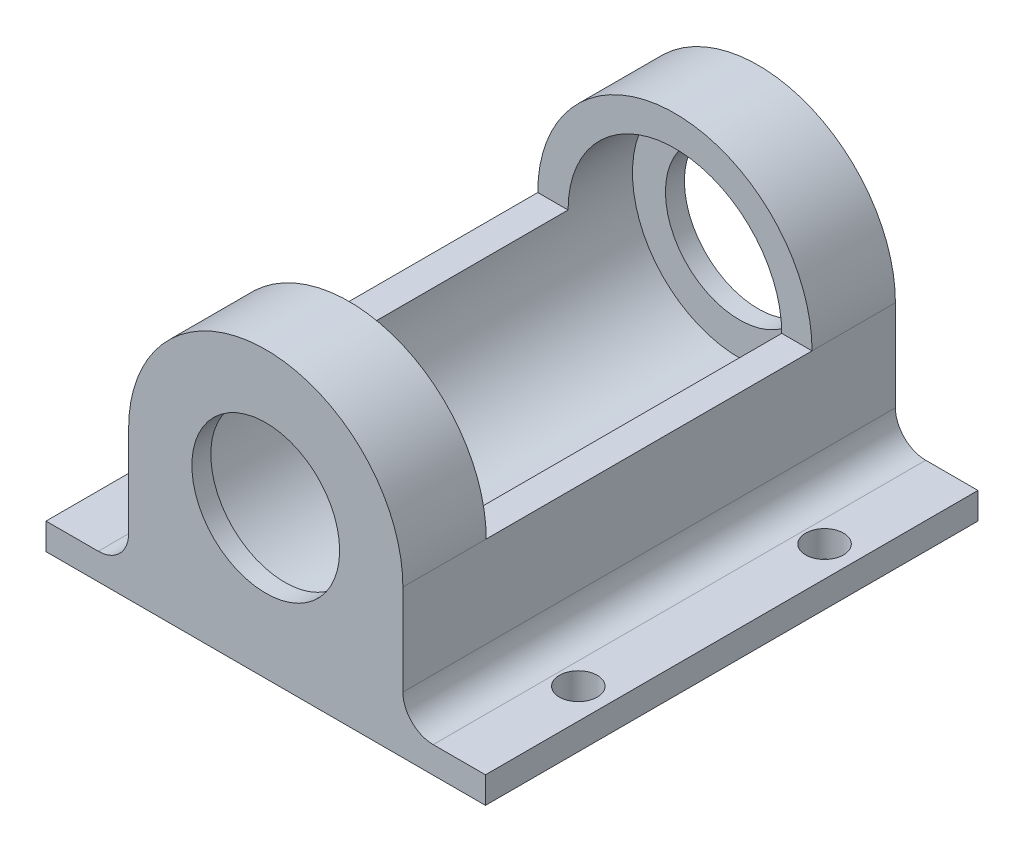
SolidWorks part; units mm, degrees
ref_plane "Front Plane" through (0, 0, 0) normal (0, 0, 1) x (1, 0, 0)
ref_plane "Top Plane" through (0, 0, 0) normal (0, 1, 0) x (1, 0, 0)
ref_plane "Right Plane" through (0, 0, 0) normal (1, 0, 0) x (0, 0, -1)
sketch "Sketch1" plane through (0, 0, 0) normal (0, 1, 0) x (1, 0, 0)
  line L0 (-43.3727, 0) -> (41.7261, 0) construction
  line L1 (-29, -32.5) -> (29, -32.5)
  line L2 (-29, -32.5) -> (-29, 32.5)
  line L3 (-29, 32.5) -> (29, 32.5)
  line L4 (29, -32.5) -> (29, 32.5)
  line L5 (-29, -32.5) -> (29, 32.5) construction
  line L6 (-29, 32.5) -> (29, -32.5) construction
  line L7 (-29, -16.25) -> (29, -16.25) construction
  line L8 (-29, 16.25) -> (29, 16.25) construction
  circle A0 centre (-25, -16.25) radius 2.5
  circle A1 centre (25, -16.25) radius 2.5
  circle A2 centre (25, 16.25) radius 2.5
  circle A3 centre (-25, 16.25) radius 2.5
  point P0 (0, 0)
  dimension "D3" = 5
  dimension "D5" = 5
  dimension "D11" = 5
  dimension "D12" = 5
  dimension "D1" = 65
  dimension "D2" = 58
  dimension "D4" = 4
  dimension "D6" = 4
  dimension "D7" = 16.25
  dimension "D8" = 16.25
  dimension "D9" = 4
  dimension "D10" = 4
extrude "Boss-Extrude1" add sketch "Sketch1" along normal blind 3.5
sketch "Sketch2" plane through (0, 0, 32.5) normal (0, 0, 1) x (1, 0, 0)
  line L0 (0, -11.0181) -> (0, 49.5169) construction
  line L1 (-29, 3.5) -> (29, 3.5) construction
  line L2 (-41.9601, 19.5) -> (50.3847, 19.5) construction
  line L3 (-18.1, 19.5) -> (-18.1, 3.5)
  line L4 (18.1, 19.5) -> (18.1, 3.5)
  circle A0 centre (0, 19.5) radius 14.1
  circle A1 centre (0, 19.5) radius 9.75
  arc A2 (-18.1, 19.5) -> (18.1, 19.5) centre (0, 19.5) cw
  line M5 (29, 3.5) -> (-29, 3.5)
  dimension "D1" = 28.2
  dimension "D3" = 19.5
  dimension "D6" = 4
  dimension "D2" = 16
extrude "Boss-Extrude2" add sketch "Sketch2" against normal blind 2.5 contours A2 L3 L4 A0 M5 | A0 A1 region at (0, 37.1027, 32.5) region at (-13.7012, 19.5, 32.5)
extrude "Boss-Extrude3" add sketch "Sketch2<3>" against normal blind 11 contours A2 L3 L4 A0 M5 region at (0, 37.1027, 32.5)
sketch "Sketch2<3>" plane through (0, 0, 32.5) normal (0, 0, 1) x (1, 0, 0) same geometry as "Sketch2"
extrude "Boss-Extrude4" add sketch "Sketch2<4>" along normal blind 11 from offset 65 contours A2 L3 L4 A0 M5 region at (0, 37.1027, 32.5) offset against normal yes
sketch "Sketch2<4>" plane through (0, 0, 32.5) normal (0, 0, 1) x (1, 0, 0) same geometry as "Sketch2"
extrude "Boss-Extrude5" add sketch "Sketch2<5>" along normal blind 2.5 from surface contours A0 A1 region at (-13.7012, 19.5, 32.5) starting at face at (0, 8.8875, -32.5)
sketch "Sketch2<5>" plane through (0, 0, 32.5) normal (0, 0, 1) x (1, 0, 0) same geometry as "Sketch2"
fillet "Fillet3" radius 4 4 edges at (-18.1, 3.5, 27) (-18.1, 3.5, -27) (18.1, 3.5, 27) (18.1, 3.5, -27)
sketch "Sketch6" plane through (0, 0, -21.5) normal (0, 0, 1) x (1, 0, 0)
  line L0 (-18.1, 7.5) -> (-18.1, 19.5)
  line L1 (-18.1, 19.5) -> (-14.1, 19.5)
  line L2 (14.1, 19.5) -> (18.1, 19.5)
  line L3 (18.1, 7.5) -> (18.1, 19.5)
  line L4 (22.1, 3.5) -> (-22.1, 3.5) construction
  line L5 (-22.1, 3.5) -> (22.1, 3.5)
  circle A0 centre (0, 19.5) radius 14.1 construction
  arc A1 (-14.1, 19.5) -> (14.1, 19.5) centre (0, 19.5) ccw
  arc A2 (-18.1, 7.5) -> (-22.1, 3.5) centre (-22.1, 7.5) cw
  arc A3 (22.1, 3.5) -> (18.1, 7.5) centre (22.1, 7.5) cw
  arc A4 (18.1, 7.5) -> (22.1, 3.5) centre (22.1, 7.5) ccw construction
extrude "Boss-Extrude6" add sketch "Sketch6" along normal through all
